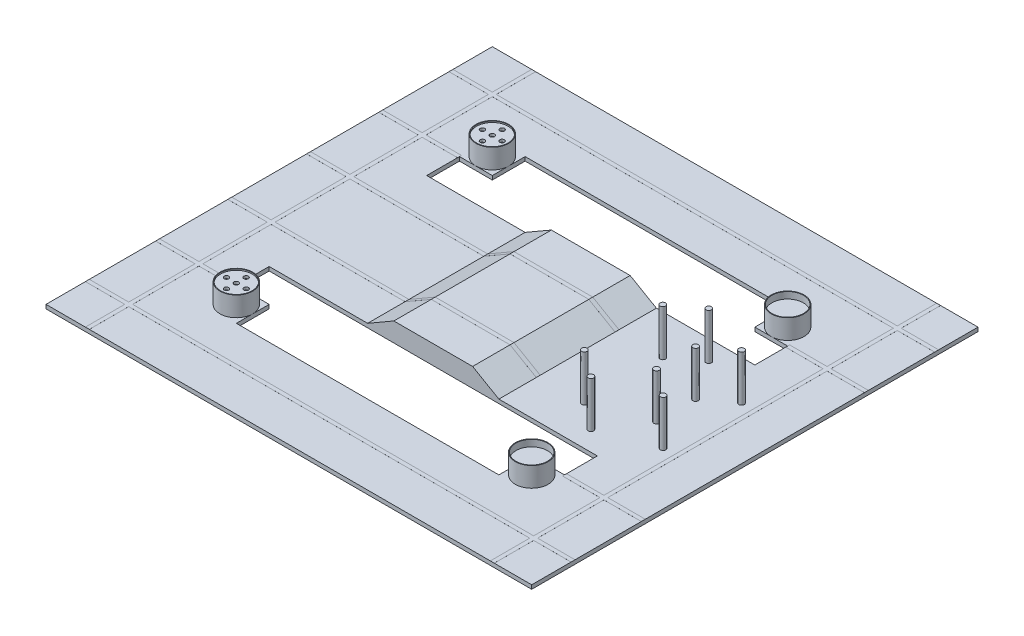
SolidWorks part; units mm, degrees
ref_plane "Front Plane" through (0, 0, 0) normal (0, 0, 1) x (1, 0, 0)
ref_plane "Top Plane" through (0, 0, 0) normal (0, 1, 0) x (1, 0, 0)
ref_plane "Right Plane" through (0, 0, 0) normal (1, 0, 0) x (0, 0, -1)
sketch "Sketch1" plane through (0, 0, 0) normal (0, 1, 0) x (1, 0, 0)
  line L0 (0, 1700) -> (0, -1700) construction
  line L1 (-1850, 1700) -> (1850, 1700)
  line L2 (-1850, 1700) -> (-1850, -1700)
  line L3 (-1850, -1700) -> (1850, -1700)
  line L4 (1850, 1700) -> (1850, -1700)
  line L5 (-1850, 0) -> (1850, 0) construction
  line L6 (-1250, -600) -> (1250, -600)
  line L7 (-1250, 1100) -> (1250, 1100)
  line L8 (-1250, 1100) -> (-1250, 600)
  line L9 (-1250, 600) -> (1250, 600)
  line L10 (1250, 1100) -> (1250, 600)
  line L11 (1250, -1100) -> (1250, -600)
  line L12 (-1250, -1100) -> (1250, -1100)
  line L13 (-1250, -1100) -> (-1250, -600)
  line L14 (1250, 850) -> (1000, 850)
  line L15 (-1250, 1100) -> (-1000, 1100)
  line L16 (-1250, 1100) -> (-1250, 850)
  line L17 (-1250, 850) -> (-1000, 850)
  line L18 (-1000, 1100) -> (-1000, 850)
  line L19 (1000, 1100) -> (1000, 850)
  line L20 (1000, -1100) -> (1000, -850)
  line L21 (1250, -850) -> (1000, -850)
  line L22 (-1250, -850) -> (-1000, -850)
  line L23 (-1000, -1100) -> (-1000, -850)
  dimension "D1" = 3700
  dimension "D2" = 3400
  dimension "D3" = 500
  dimension "D4" = 2500
  dimension "D5" = 600
  dimension "D6" = 600
  dimension "D7" = 250
  dimension "D8" = 250
extrude "Boss-Extrude1" add sketch "Sketch1" along normal blind 30 contours L4 L1 L2 L3 L7 L10 L9 L8 L12 L13 L6 L11 | L18 L7 L8 L17 | L7 L19 L14 L10 | L11 L21 L20 L12 | L12 L23 L22 L13 region at (0, 0, 0) region at (-1125, 0, 975) region at (1125, 0, 975) region at (-1125, 0, -975) region at (1125, 0, -975)
sketch "Sketch2" plane through (0, 0, 0) normal (0, 0, 1) x (1, 0, 0)
  line L0 (-500, 30) -> (-300, 145.4701)
  line L1 (-1850, 30) -> (1850, 30) construction
  line L2 (-300, 145.4701) -> (300, 145.4701)
  line L3 (300, 145.4701) -> (500, 30)
  line L4 (500, 30) -> (-500, 30)
  line L5 (0, 145.4701) -> (0, 30) construction
  dimension "D1" = 200
  dimension "D2" = 600
  dimension "D3" = 30
extrude "Boss-Extrude2" add sketch "Sketch2" along normal mid plane 1200
sketch "Sketch3" plane through (0, 30, 0) normal (0, 1, 0) x (1, 0, 0)
  line L0 (-1125, 850) -> (-1125, 1042.2639) construction
  line L1 (-1250, 850) -> (-1000, 850) construction
  line L2 (-1000, 975) -> (-1165.3308, 975) construction
  line L3 (-1000, 1100) -> (-1000, 850) construction
  circle A0 centre (-1125, 975) radius 125
extrude "Boss-Extrude3" add sketch "Sketch3" along normal blind 150
sketch "Sketch4" plane through (0, 180, 0) normal (0, 1, 0) x (1, 0, 0)
  circle A0 centre (-1125, 975) radius 120
  dimension "D1" = 240
extrude "Cut-Extrude1" cut sketch "Sketch4" against normal blind 10
sketch "Sketch5" plane through (0, 170, 0) normal (0, 1, 0) x (1, 0, 0)
  line L0 (-1005, 975) -> (-1245, 975) construction
  line L1 (-1125, 1095) -> (-1125, 855) construction
  circle A0 centre (-1125, 975) radius 120 construction
  circle A1 centre (-1125, 975) radius 120 construction
  circle A2 centre (-1125, 975) radius 17.5
  circle A3 centre (-1050, 975) radius 17.5
  circle A4 centre (-1125, 900) radius 17.5
  circle A5 centre (-1200, 975) radius 17.5
  circle A6 centre (-1125, 1050) radius 17.5
  dimension "D1" = 35
  dimension "D2" = 75
  dimension "D3" = 75
  dimension "D4" = 75
  dimension "D5" = 75
extrude "Cut-Extrude2" cut sketch "Sketch5" against normal blind 20
mirror "Mirror2" about plane through (0, 0, 0) normal (0, 0, 1) of "Boss-Extrude3", "Cut-Extrude1", "Cut-Extrude2"
mirror "Mirror3" about plane through (0, 0, 0) normal (1, 0, 0) of "Mirror2"
sketch "Sketch6" plane through (0, 170, 0) normal (0, 1, 0) x (1, 0, 0)
  circle A0 centre (1125, 975) radius 120
extrude "Cut-Extrude3" cut sketch "Sketch6" against normal blind 40
mirror "Mirror4" about plane through (0, 0, 0) normal (0, 0, 1) of "Cut-Extrude3"
sketch "Sketch7" plane through (0, 30, 0) normal (0, 1, 0) x (1, 0, 0)
  line L1 (-1850, 1700) -> (-1550, 1700)
  line L2 (-1850, 1700) -> (-1850, 1400)
  line L3 (-1850, 1400) -> (-1550, 1400)
  line L4 (-1550, 1700) -> (-1550, 1400)
  line L5 (-1850, -1700) -> (-1550, -1700)
  line L6 (-1850, -1700) -> (-1850, -1400)
  line L7 (-1850, -1400) -> (-1550, -1400)
  line L8 (-1550, -1700) -> (-1550, -1400)
  dimension "D1" = 300
extrude "Boss-Extrude4" add sketch "Sketch7" along normal blind 0.1
sketch "Sketch8" plane through (0, 30, 0) normal (0, 1, 0) x (1, 0, 0)
  line L0 (-1850, 1385) -> (1850, 1385)
  line L1 (-1850, 1400) -> (-1850, -1400) construction
  line L2 (1850, 1700) -> (1850, -1700) construction
  line L3 (-1535, 1700) -> (-1535, -1700)
  line L4 (-1550, 1700) -> (1850, 1700) construction
  line L5 (-1550, -1700) -> (1850, -1700) construction
  line L6 (1550, 1700) -> (1550, -1700)
  line L7 (-1250, 850) -> (-1850, 850)
  line L8 (-1850, 300) -> (500, 300)
  line L9 (-1850, -300) -> (500, -300)
  line L10 (-1850, -1385) -> (1850, -1385)
  line L11 (-1250, -850) -> (-1850, -850)
  line L12 (-1850, 1400) -> (-1550, 1400) construction
  line L13 (-1550, 1400) -> (-1550, 1700) construction
  line L14 (-1250, -600) -> (-500, -600) construction
  line L15 (-1250, 600) -> (-500, 600) construction
  line L16 (-1550, -1400) -> (-1850, -1400) construction
  line L17 (1250, 850) -> (1850, 850)
  line L18 (1250, -850) -> (1850, -850)
  line L19 (500, 600) -> (500, -600) construction
  dimension "D1" = 15
  dimension "D2" = 15
  dimension "D3" = 300
  dimension "D4" = 300
  dimension "D5" = 300
  dimension "D6" = 15
extrude "Extrude-Thin1" add sketch "Sketch8" along normal blind 0.2 thin contours L0 | L3 | L7 | L8 | L9 | L11 | L10 | L6 | L17 | L18 thin type mid plane wall 30
sketch "Sketch9" plane through (-137.9904, 239.0064, 0) normal (-0.5, 0.866, 0) x (0.866, 0.5, 0)
  line L0 (-417.8127, 300) -> (-187.0726, 300)
  line L1 (-417.8127, 285) -> (-417.8127, 315) construction
  line L2 (-187.0726, -600) -> (-187.0726, 600) construction
  line L3 (-417.8127, -300) -> (-187.0726, -300)
  line L4 (-417.8127, -315) -> (-417.8127, -285) construction
extrude "Extrude-Thin2" add sketch "Sketch9" along normal blind 0.1 thin contours L0 | L3 thin type mid plane wall 30
sketch "Sketch10" plane through (0, 145.4701, 0) normal (0, 1, 0) x (1, 0, 0)
  line L0 (-300, 300) -> (300, 300)
  line L1 (-300, 315) -> (-300, 285) construction
  line L2 (300, -600) -> (300, 600) construction
  line L3 (-300, -300) -> (300, -300)
  line L4 (-300, -285) -> (-300, -315) construction
extrude "Extrude-Thin3" add sketch "Sketch10" along normal blind 0.1 thin contours L0 | L3 thin type mid plane wall 30
mirror "Mirror5" about plane through (0, 0, 0) normal (1, 0, 0) of "Extrude-Thin2"
sketch "Sketch11" plane through (0, 30, 0) normal (0, 1, 0) x (1, 0, 0)
  line L0 (500, 0) -> (1467.7975, 0) construction
  line L1 (500, -285) -> (500, 285) construction
  line L2 (500, -600) -> (500, -315) construction
  circle A0 centre (850, -298.837) radius 21
  circle A1 centre (1050, -448.837) radius 21
  circle A2 centre (1450, -298.837) radius 21
  circle A3 centre (1250, -148.837) radius 21
  dimension "D1" = 42
  dimension "D2" = 350
  dimension "D3" = 200
  dimension "D4" = 200
  dimension "D5" = 200
  dimension "D6" = 150
  dimension "D7" = 150
  dimension "D8" = 150
extrude "Boss-Extrude5" add sketch "Sketch11" along normal blind 350
mirror "Mirror6" about plane through (0, 0, 0) normal (0, 0, 1) of "Boss-Extrude5"
